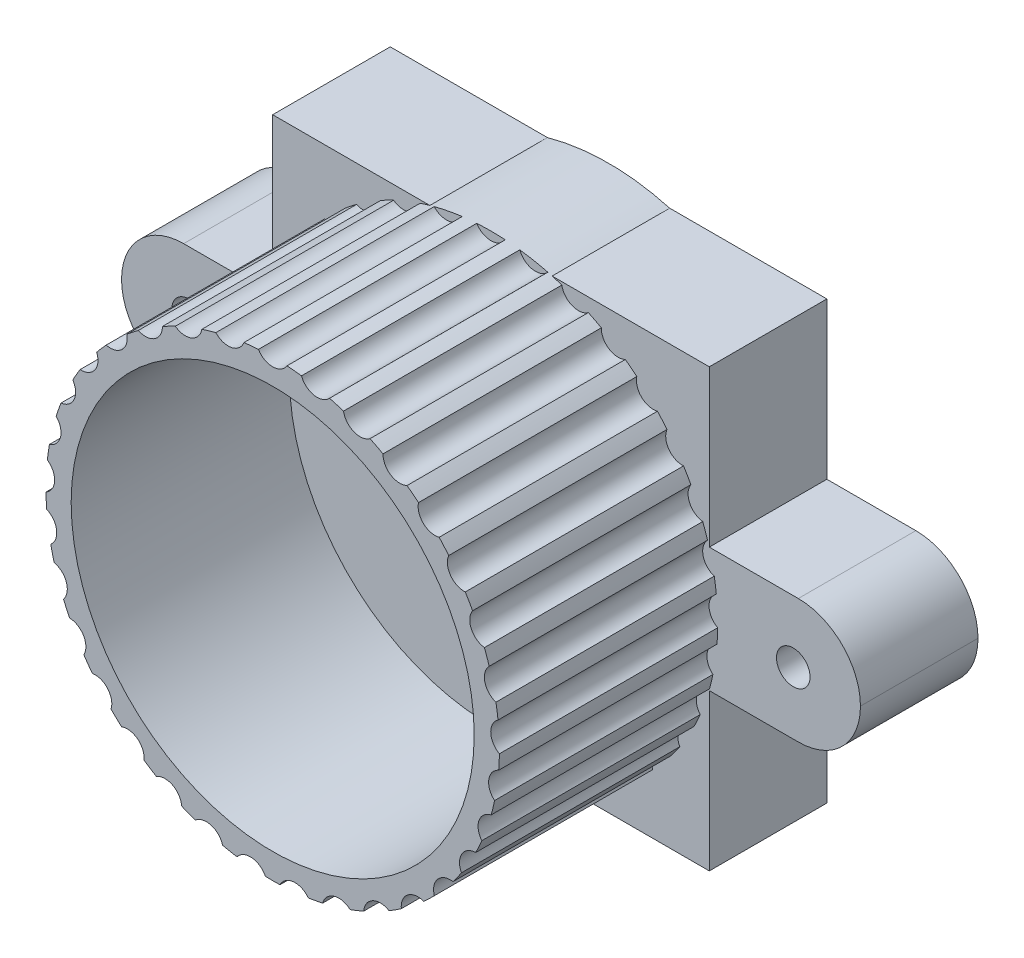
SolidWorks part; units mm, degrees
ref_plane "Front Plane" through (0, 0, 0) normal (0, 0, 1) x (1, 0, 0)
ref_plane "Top Plane" through (0, 0, 0) normal (0, 1, 0) x (1, 0, 0)
ref_plane "Right Plane" through (0, 0, 0) normal (1, 0, 0) x (0, 0, -1)
sketch "Sketch1" plane through (0, 0, 0) normal (0, 0, 1) x (1, 0, 0)
  line L1 (-6.5, 6.5) -> (6.5, 6.5)
  line L2 (-6.5, 6.5) -> (-6.5, -6.5)
  line L3 (-6.5, -6.5) -> (6.5, -6.5)
  line L4 (6.5, 6.5) -> (6.5, -6.5)
  line L5 (-6.5, 6.5) -> (6.5, -6.5) construction
  line L6 (-6.5, -6.5) -> (6.5, 6.5) construction
  point P0 (0, 0)
  dimension "D1" = 13
  dimension "D2" = 13
extrude "Boss-Extrude1" add sketch "Sketch1" along normal blind 3.5
sketch "Sketch2" plane through (0, 0, 3.5) normal (0, 0, 1) x (1, 0, 0)
  line L1 (-11, 1.85) -> (11, 1.85)
  line L2 (-11, 1.85) -> (-11, -1.85)
  line L3 (-11, -1.85) -> (11, -1.85)
  line L4 (11, 1.85) -> (11, -1.85)
  line L5 (-11, 1.85) -> (11, -1.85) construction
  line L6 (-11, -1.85) -> (11, 1.85) construction
  point P0 (0, 0)
  dimension "D1" = 22
  dimension "D2" = 3.7
extrude "Boss-Extrude2" add sketch "Sketch2" against normal blind 3.5
fillet "Fillet1" radius 1.85 4 edges at (11, -1.85, 1.75) (11, 1.85, 1.75) (-11, -1.85, 1.75) (-11, 1.85, 1.75)
sketch "Sketch3" plane through (0, 0, 3.5) normal (0, 0, 1) x (1, 0, 0)
  circle A0 centre (-9, 0) radius 0.5
  circle A1 centre (9, 0) radius 0.5
  dimension "D1" = 1
  dimension "D2" = 1
  dimension "D3" = 18
  dimension "D4" = 9
extrude "Cut-Extrude1" cut sketch "Sketch3" against normal blind 3.5
sketch "Sketch4" plane through (0, 0, 3.5) normal (0, 0, 1) x (1, 0, 0)
  circle A0 centre (0, 0) radius 6.75
  dimension "D1" = 13.5
extrude "Boss-Extrude3" add sketch "Sketch4" along normal blind 6.5 and the other way blind 3.5
sketch "Sketch5" plane through (0, 0, 10) normal (0, 0, 1) x (1, 0, 0)
  circle A0 centre (0, 7) radius 0.5
  circle A1 centre (1.3248, 6.8735) radius 0.5
  circle A2 centre (2.6016, 6.4986) radius 0.5
  circle A3 centre (3.7845, 5.8888) radius 0.5
  circle A4 centre (4.8306, 5.0661) radius 0.5
  circle A5 centre (5.702, 4.0604) radius 0.5
  circle A6 centre (6.3674, 2.9079) radius 0.5
  circle A7 centre (6.8027, 1.6503) radius 0.5
  circle A8 centre (6.9921, 0.3331) radius 0.5
  circle A9 centre (6.9288, -0.9962) radius 0.5
  circle A10 centre (6.615, -2.2895) radius 0.5
  circle A11 centre (6.0622, -3.5) radius 0.5
  circle A12 centre (5.2902, -4.584) radius 0.5
  circle A13 centre (4.3271, -5.5024) radius 0.5
  circle A14 centre (3.2076, -6.2218) radius 0.5
  circle A15 centre (1.9721, -6.7165) radius 0.5
  circle A16 centre (0.6654, -6.9683) radius 0.5
  circle A17 centre (-0.6654, -6.9683) radius 0.5
  circle A18 centre (-1.9721, -6.7165) radius 0.5
  circle A19 centre (-3.2076, -6.2218) radius 0.5
  circle A20 centre (-4.3271, -5.5024) radius 0.5
  circle A21 centre (-5.2902, -4.584) radius 0.5
  circle A22 centre (-6.0622, -3.5) radius 0.5
  circle A23 centre (-6.615, -2.2895) radius 0.5
  circle A24 centre (-6.9288, -0.9962) radius 0.5
  circle A25 centre (-6.9921, 0.3331) radius 0.5
  circle A26 centre (-6.8027, 1.6503) radius 0.5
  circle A27 centre (-6.3674, 2.9079) radius 0.5
  circle A28 centre (-5.702, 4.0604) radius 0.5
  circle A29 centre (-4.8306, 5.0661) radius 0.5
  circle A30 centre (-3.7845, 5.8888) radius 0.5
  circle A31 centre (-2.6016, 6.4986) radius 0.5
  circle A32 centre (-1.3248, 6.8735) radius 0.5
  point P69 (0, 0)
  dimension "D1" = 1
  dimension "D2" = 7
  dimension "D3" = 33
extrude "Cut-Extrude2" cut sketch "Sketch5" against normal blind 6.5
sketch "Sketch6" plane through (0, 0, 10) normal (0, 0, 1) x (1, 0, 0)
  circle A0 centre (0, 0) radius 6
  dimension "D1" = 12
extrude "Cut-Extrude3" cut sketch "Sketch6" against normal blind 6.5
